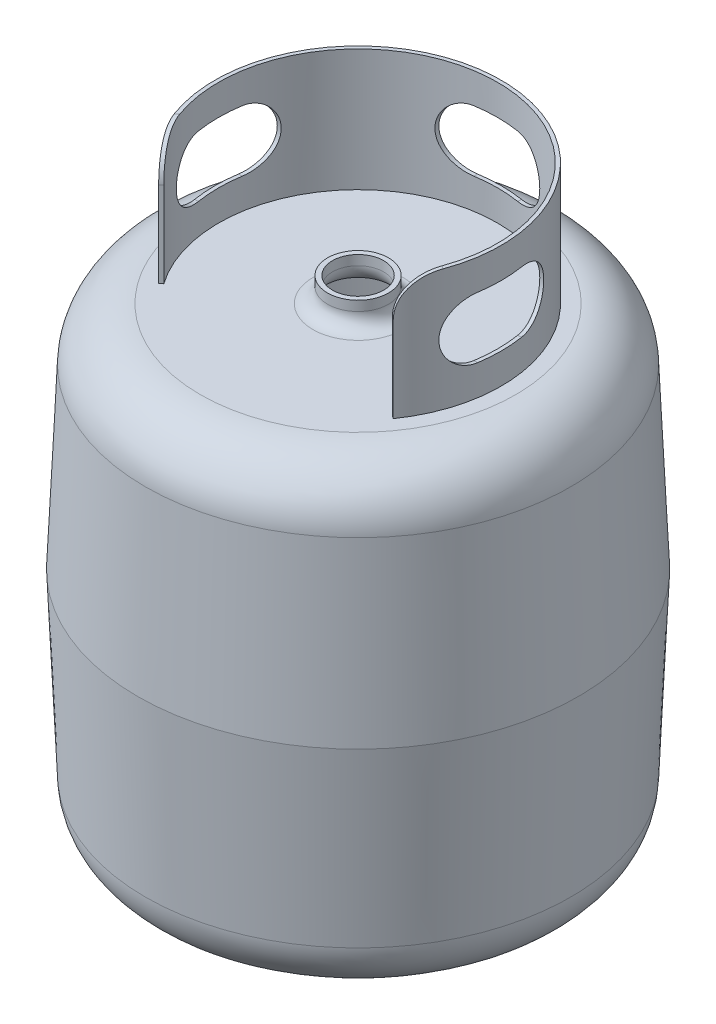
SolidWorks part; units mm, degrees
material "1060 Alloy"
ref_plane "Front Plane" through (0, 0, 0) normal (0, 0, 1) x (1, 0, 0)
ref_plane "Top Plane" through (0, 0, 0) normal (0, 1, 0) x (1, 0, 0)
ref_plane "Right Plane" through (0, 0, 0) normal (1, 0, 0) x (0, 0, -1)
sketch "Sketch1" plane through (0, 0, 0) normal (1, 0, 0) x (0, 0, -1)
  line L0 (0, 0) -> (0, -397.5) construction
  line L1 (-25, -8) -> (-25, 0)
  line L2 (-37, -20) -> (-129.4219, -20)
  line L3 (-174.379, -63.0371) -> (-180.741, -208.75)
  line L4 (-180.741, -208.75) -> (-174.379, -354.4629)
  line L5 (-129.4219, -397.5) -> (0, -397.5)
  line L6 (0, 0) -> (0, -397.5)
  line L7 (-25, 0) -> (0, 0)
  arc A0 (-25, -8) -> (-37, -20) centre (-37, -8) cw
  arc A1 (-174.379, -354.4629) -> (-129.4219, -397.5) centre (-129.4219, -352.5) ccw
  arc A2 (-129.4219, -20) -> (-174.379, -63.0371) centre (-129.4219, -65) ccw
  point P11 (-172.5, -397.5)
  point P14 (-172.5, -20)
  dimension "D2" = 12
  dimension "D8" = 45
  dimension "D1" = 25
  dimension "D3" = 172.5
  dimension "D4" = 172.5
  dimension "D5" = 92.5
  dimension "D6" = 92.5
  dimension "D7" = 397.5
  dimension "D9" = 20
revolve "Revolve2" add sketch "Sketch1" angle 360 about L6
shell "Shell2" thickness 4 removed face at (0, 0, 25)
sketch "Sketch2" plane through (0, -20, 0) normal (0, 1, 0) x (1, 0, 0)
  line L0 (0, 0) -> (0, -114.4219) construction
  line L1 (0, 0) -> (96.1864, -67.3504)
  line L2 (0, 0) -> (-96.1864, -67.3504)
  arc A0 (96.1864, -67.3504) -> (-96.1864, -67.3504) centre (0, 0) ccw
  arc A1 (93.7289, -65.6297) -> (-93.7289, -65.6297) centre (0, 0) ccw
  circle A2 centre (0, 0) radius 129.4219 construction
  dimension "D1" = 3
  dimension "D2" = 12
  dimension "D3" = 55
extrude "Boss-Extrude1" add sketch "Sketch2" along normal blind 100 contours A1 L1 A0 L2 region at (0, -20, -117.4101)
fillet "Fillet1" radius 30 2 edges at (-94.9576, 80, 66.4901) (94.9576, 80, 66.4901)
sketch "Sketch4" plane through (0, 0, 0) normal (1, 0, 0) x (0, 0, -1)
  line L0 (-18, 5) -> (18, 5)
  line L1 (18, 55) -> (-18, 55)
  line L2 (0, 55) -> (0, 5) construction
  line L3 (0, 0) -> (0, 5) construction
  line L4 (114.4219, 80) -> (-38.7592, 80) construction
  arc A0 (18, 5) -> (18, 55) centre (18, 30) ccw
  arc A1 (-18, 55) -> (-18, 5) centre (-18, 30) ccw
  point P12 (0, 30)
  point P13 (43, 30)
  point P14 (-43, 30)
  dimension "D3" = 50
  dimension "D1" = 50
  dimension "D2" = 18
extrude "Cut-Extrude1" cut sketch "Sketch4" against normal through all both and the other way through all
pattern_circular "CirPattern1" count 4 over 360 about axis through (0, 80, 0) along (0, 1, 0) of "Cut-Extrude1"
equation "\"A\"= 345.00"
equation "\"B\"= 397.50"
